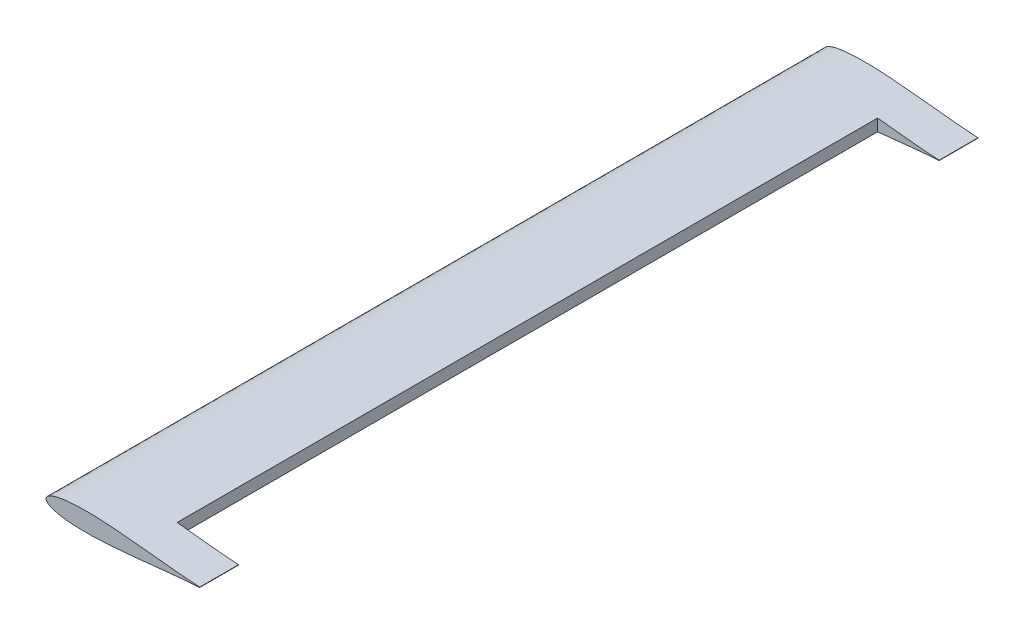
SolidWorks part; units mm, degrees
other "Markup1"
sketch "Sketch3" plane through (-0.0553, -7.355, 609.6) normal (0, 0, 1) x (1, 0, 0)
ref_plane "Front Plane" through (0, 0, 0) normal (0, 0, 1) x (1, 0, 0)
ref_plane "Top Plane" through (0, 0, 0) normal (0, 1, 0) x (1, 0, 0)
ref_plane "Right Plane" through (0, 0, 0) normal (1, 0, 0) x (0, 0, -1)
curve "Curve1"
  spline degree 3 poles (25.3337, -0.0003, 0) (25.4166, 0, 0) (25.3337, 0.0003, 0) (25.2654, 0.0018, 0) (25.098, 0.0055, 0) (24.8899, 0.0127, 0) (24.614, 0.0243, 0) (24.2833, 0.0411, 0) (23.8951, 0.064, 0) (23.4526, 0.0935, 0) (22.9577, 0.1302, 0) (22.4128, 0.1742, 0) (21.8206, 0.2257, 0) (21.184, 0.2845, 0) (20.5061, 0.3502, 0) (19.7901, 0.4224, 0) (19.0396, 0.5004, 0) (18.2582, 0.5832, 0) (17.4498, 0.6697, 0) (16.6182, 0.7589, 0) (15.7675, 0.8494, 0) (14.9019, 0.9396, 0) (14.0255, 1.0282, 0) (13.1427, 1.1135, 0) (12.2578, 1.1941, 0) (11.3749, 1.2683, 0) (10.4986, 1.3345, 0) (9.6329, 1.3915, 0) (8.7821, 1.4377, 0) (7.9504, 1.4721, 0) (7.1418, 1.4935, 0) (6.3603, 1.501, 0) (5.6096, 1.4941, 0) (4.8934, 1.4721, 0) (4.2152, 1.4349, 0) (3.5783, 1.3824, 0) (2.9857, 1.3149, 0) (2.4403, 1.233, 0) (1.9447, 1.1371, 0) (1.5013, 1.0283, 0) (1.1121, 0.9078, 0) (0.7787, 0.7769, 0) (0.5025, 0.6369, 0) (0.2843, 0.4891, 0) (0.1244, 0.334, 0) (0.024, 0.1711, 0) (-0.0113, 0, 0) (0.024, -0.1711, 0) (0.1244, -0.334, 0) (0.2843, -0.4891, 0) (0.5025, -0.6369, 0) (0.7787, -0.7769, 0) (1.1121, -0.9078, 0) (1.5013, -1.0283, 0) (1.9447, -1.1371, 0) (2.4403, -1.233, 0) (2.9857, -1.3149, 0) (3.5783, -1.3824, 0) (4.2152, -1.4349, 0) (4.8934, -1.4721, 0) (5.6096, -1.4941, 0) (6.3603, -1.501, 0) (7.1418, -1.4935, 0) (7.9504, -1.4721, 0) (8.7821, -1.4377, 0) (9.6329, -1.3915, 0) (10.4986, -1.3345, 0) (11.3749, -1.2683, 0) (12.2578, -1.1941, 0) (13.1427, -1.1135, 0) (14.0255, -1.0282, 0) (14.9019, -0.9396, 0) (15.7675, -0.8494, 0) (16.6182, -0.7589, 0) (17.4498, -0.6697, 0) (18.2582, -0.5832, 0) (19.0396, -0.5004, 0) (19.7901, -0.4224, 0) (20.5061, -0.3502, 0) (21.184, -0.2845, 0) (21.8206, -0.2257, 0) (22.4128, -0.1742, 0) (22.9577, -0.1302, 0) (23.4526, -0.0935, 0) (23.8951, -0.064, 0) (24.2833, -0.0411, 0) (24.614, -0.0243, 0) (24.8899, -0.0127, 0) (25.098, -0.0055, 0) (25.2654, -0.0018, 0) (25.3337, -0.0003, 0) (25.4166, 0, 0) (25.3337, 0.0003, 0) knots -0.005355 -0.002385 -0.000597 0 0.000597 0.002385 0.005355 0.009495 0.014784 0.021198 0.028708 0.037278 0.046868 0.05743 0.068917 0.081271 0.094432 0.108338 0.122919 0.138103 0.153815 0.169978 0.186509 0.203327 0.220349 0.237488 0.25466 0.271779 0.288763 0.305527 0.32199 0.338073 0.353702 0.368803 0.383306 0.397149 0.410269 0.422614 0.434133 0.444783 0.454527 0.463337 0.471194 0.478092 0.484042 0.489082 0.493295 0.496842 0.5 0.503158 0.506705 0.510918 0.515958 0.521908 0.528806 0.536663 0.545473 0.555218 0.565867 0.577386 0.589731 0.602851 0.616694 0.631197 0.646298 0.661927 0.67801 0.694473 0.711237 0.728221 0.74534 0.762512 0.779651 0.796673 0.813491 0.830023 0.846185 0.861897 0.877081 0.891662 0.905568 0.918729 0.931083 0.94257 0.953133 0.962722 0.971292 0.978802 0.985216 0.990505 0.994645 0.997615 0.999403 1 1.000597 1.002385 1.005355 periodic
sketch "Sketch2" plane through (0, 0, 0) normal (0, 0, 1) x (1, 0, 0)
  line L0 (0, 0) -> (25.4, 0) construction
  line L1 (0, 0) -> (124.46, 0) construction
  line L2 (120.381, 0.1319) -> (120.381, -0.1319)
  line L3 (62.23, 0) -> (62.23, 5.6527) construction
  spline S0 degree 3 poles (25.3337, -0.0003) (25.4166, 0) (25.3337, 0.0003) (25.2654, 0.0018) (25.098, 0.0055) (24.8899, 0.0127) (24.614, 0.0243) (24.2833, 0.0411) (23.8951, 0.064) (23.4526, 0.0935) (22.9577, 0.1302) (22.4128, 0.1742) (21.8206, 0.2257) (21.184, 0.2845) (20.5061, 0.3502) (19.7901, 0.4224) (19.0396, 0.5004) (18.2582, 0.5832) (17.4498, 0.6697) (16.6182, 0.7589) (15.7675, 0.8494) (14.9019, 0.9396) (14.0255, 1.0282) (13.1427, 1.1135) (12.2578, 1.1941) (11.3749, 1.2683) (10.4986, 1.3345) (9.6329, 1.3915) (8.7821, 1.4377) (7.9504, 1.4721) (7.1418, 1.4935) (6.3603, 1.501) (5.6096, 1.4941) (4.8934, 1.4721) (4.2152, 1.4349) (3.5783, 1.3824) (2.9857, 1.3149) (2.4403, 1.233) (1.9447, 1.1371) (1.5013, 1.0283) (1.1121, 0.9078) (0.7787, 0.7769) (0.5025, 0.6369) (0.2843, 0.4891) (0.1244, 0.334) (0.024, 0.1711) (-0.0113, 0) (0.024, -0.1711) (0.1244, -0.334) (0.2843, -0.4891) (0.5025, -0.6369) (0.7787, -0.7769) (1.1121, -0.9078) (1.5013, -1.0283) (1.9447, -1.1371) (2.4403, -1.233) (2.9857, -1.3149) (3.5783, -1.3824) (4.2152, -1.4349) (4.8934, -1.4721) (5.6096, -1.4941) (6.3603, -1.501) (7.1418, -1.4935) (7.9504, -1.4721) (8.7821, -1.4377) (9.6329, -1.3915) (10.4986, -1.3345) (11.3749, -1.2683) (12.2578, -1.1941) (13.1427, -1.1135) (14.0255, -1.0282) (14.9019, -0.9396) (15.7675, -0.8494) (16.6182, -0.7589) (17.4498, -0.6697) (18.2582, -0.5832) (19.0396, -0.5004) (19.7901, -0.4224) (20.5061, -0.3502) (21.184, -0.2845) (21.8206, -0.2257) (22.4128, -0.1742) (22.9577, -0.1302) (23.4526, -0.0935) (23.8951, -0.064) (24.2833, -0.0411) (24.614, -0.0243) (24.8899, -0.0127) (25.098, -0.0055) (25.2654, -0.0018) (25.3337, -0.0003) (25.4166, 0) (25.3337, 0.0003) knots -0.005355 -0.002385 -0.000597 0 0.000597 0.002385 0.005355 0.009495 0.014784 0.021198 0.028708 0.037278 0.046868 0.05743 0.068917 0.081271 0.094432 0.108338 0.122919 0.138103 0.153815 0.169978 0.186509 0.203327 0.220349 0.237488 0.25466 0.271779 0.288763 0.305527 0.32199 0.338073 0.353702 0.368803 0.383306 0.397149 0.410269 0.422614 0.434133 0.444783 0.454527 0.463337 0.471194 0.478092 0.484042 0.489082 0.493295 0.496842 0.5 0.503158 0.506705 0.510918 0.515958 0.521908 0.528806 0.536663 0.545473 0.555218 0.565867 0.577386 0.589731 0.602851 0.616694 0.631197 0.646298 0.661927 0.67801 0.694473 0.711237 0.728221 0.74534 0.762512 0.779651 0.796673 0.813491 0.830023 0.846185 0.861897 0.877081 0.891662 0.905568 0.918729 0.931083 0.94257 0.953133 0.962722 0.971292 0.978802 0.985216 0.990505 0.994645 0.997615 0.999403 1 1.000597 1.002385 1.005355 only from (25.4, 0) to (25.4, 0) construction
  spline S1 degree 3 poles (25.3337, -0.0003) (25.4166, 0) (25.3337, 0.0003) (25.2654, 0.0018) (25.098, 0.0055) (24.8899, 0.0127) (24.614, 0.0243) (24.2833, 0.0411) (23.8951, 0.064) (23.4526, 0.0935) (22.9577, 0.1302) (22.4128, 0.1742) (21.8206, 0.2257) (21.184, 0.2845) (20.5061, 0.3502) (19.7901, 0.4224) (19.0396, 0.5004) (18.2582, 0.5832) (17.4498, 0.6697) (16.6182, 0.7589) (15.7675, 0.8494) (14.9019, 0.9396) (14.0255, 1.0282) (13.1427, 1.1135) (12.2578, 1.1941) (11.3749, 1.2683) (10.4986, 1.3345) (9.6329, 1.3915) (8.7821, 1.4377) (7.9504, 1.4721) (7.1418, 1.4935) (6.3603, 1.501) (5.6096, 1.4941) (4.8934, 1.4721) (4.2152, 1.4349) (3.5783, 1.3824) (2.9857, 1.3149) (2.4403, 1.233) (1.9447, 1.1371) (1.5013, 1.0283) (1.1121, 0.9078) (0.7787, 0.7769) (0.5025, 0.6369) (0.2843, 0.4891) (0.1244, 0.334) (0.024, 0.1711) (-0.0113, 0) (0.024, -0.1711) (0.1244, -0.334) (0.2843, -0.4891) (0.5025, -0.6369) (0.7787, -0.7769) (1.1121, -0.9078) (1.5013, -1.0283) (1.9447, -1.1371) (2.4403, -1.233) (2.9857, -1.3149) (3.5783, -1.3824) (4.2152, -1.4349) (4.8934, -1.4721) (5.6096, -1.4941) (6.3603, -1.501) (7.1418, -1.4935) (7.9504, -1.4721) (8.7821, -1.4377) (9.6329, -1.3915) (10.4986, -1.3345) (11.3749, -1.2683) (12.2578, -1.1941) (13.1427, -1.1135) (14.0255, -1.0282) (14.9019, -0.9396) (15.7675, -0.8494) (16.6182, -0.7589) (17.4498, -0.6697) (18.2582, -0.5832) (19.0396, -0.5004) (19.7901, -0.4224) (20.5061, -0.3502) (21.184, -0.2845) (21.8206, -0.2257) (22.4128, -0.1742) (22.9577, -0.1302) (23.4526, -0.0935) (23.8951, -0.064) (24.2833, -0.0411) (24.614, -0.0243) (24.8899, -0.0127) (25.098, -0.0055) (25.2654, -0.0018) (25.3337, -0.0003) (25.4166, 0) (25.3337, 0.0003) knots -0.005355 -0.002385 -0.000597 0 0.000597 0.002385 0.005355 0.009495 0.014784 0.021198 0.028708 0.037278 0.046868 0.05743 0.068917 0.081271 0.094432 0.108338 0.122919 0.138103 0.153815 0.169978 0.186509 0.203327 0.220349 0.237488 0.25466 0.271779 0.288763 0.305527 0.32199 0.338073 0.353702 0.368803 0.383306 0.397149 0.410269 0.422614 0.434133 0.444783 0.454527 0.463337 0.471194 0.478092 0.484042 0.489082 0.493295 0.496842 0.5 0.503158 0.506705 0.510918 0.515958 0.521908 0.528806 0.536663 0.545473 0.555218 0.565867 0.577386 0.589731 0.602851 0.616694 0.631197 0.646298 0.661927 0.67801 0.694473 0.711237 0.728221 0.74534 0.762512 0.779651 0.796673 0.813491 0.830023 0.846185 0.861897 0.877081 0.891662 0.905568 0.918729 0.931083 0.94257 0.953133 0.962722 0.971292 0.978802 0.985216 0.990505 0.994645 0.997615 0.999403 1 1.000597 1.002385 1.005355 only from (25.4, 0) to (25.4, 0) construction
  spline S2 degree 3 poles (120.381, 0.1319) (119.9463, 0.1527) (118.8798, 0.2078) (117.0858, 0.3137) (114.9178, 0.4584) (112.4927, 0.6382) (109.8228, 0.8537) (106.9211, 1.106) (103.8017, 1.394) (100.4797, 1.7159) (96.9715, 2.0698) (93.294, 2.4518) (89.4653, 2.8575) (85.5038, 3.2818) (81.4291, 3.7187) (77.2608, 4.162) (73.0193, 4.6041) (68.7252, 5.0383) (64.3994, 5.4564) (60.0631, 5.8512) (55.7372, 6.2145) (51.4429, 6.5392) (47.2011, 6.8181) (43.0324, 7.0448) (38.9571, 7.2131) (34.9951, 7.3181) (31.1655, 7.355) (27.4872, 7.3209) (23.9779, 7.2133) (20.6546, 7.0309) (17.5336, 6.7739) (14.6298, 6.4432) (11.9574, 6.0415) (9.5291, 5.5718) (7.3563, 5.0389) (5.4492, 4.4484) (3.8158, 3.8067) (2.4624, 3.1207) (1.3928, 2.3964) (0.6096, 1.6368) (0.1174, 0.8384) (-0.0553, 0) (0.1174, -0.8384) (0.6096, -1.6368) (1.3928, -2.3964) (2.4624, -3.1207) (3.8158, -3.8067) (5.4492, -4.4484) (7.3563, -5.0389) (9.5291, -5.5718) (11.9574, -6.0415) (14.6299, -6.4433) (17.5336, -6.7739) (20.6546, -7.0309) (23.9779, -7.2133) (27.4872, -7.3209) (31.1655, -7.355) (34.9951, -7.3181) (38.9571, -7.2131) (43.0324, -7.0448) (47.2011, -6.8181) (51.4429, -6.5392) (55.7372, -6.2145) (60.0631, -5.8512) (64.3994, -5.4564) (68.7252, -5.0383) (73.0193, -4.6041) (77.2608, -4.162) (81.4291, -3.7187) (85.5039, -3.2817) (89.4653, -2.8575) (93.294, -2.4518) (96.9715, -2.0698) (100.4797, -1.7159) (103.8017, -1.394) (106.9211, -1.106) (109.8228, -0.8537) (112.4927, -0.6382) (114.9179, -0.4584) (117.0858, -0.3137) (118.8798, -0.2078) (119.9463, -0.1527) (120.381, -0.1319) knots 0.016066 0.016066 0.016066 0.016066 0.021198 0.028708 0.037278 0.046868 0.05743 0.068917 0.081271 0.094432 0.108338 0.122919 0.138103 0.153815 0.169978 0.186509 0.203327 0.220349 0.237488 0.25466 0.271779 0.288763 0.305527 0.32199 0.338073 0.353702 0.368803 0.383306 0.397149 0.410269 0.422614 0.434133 0.444783 0.454527 0.463337 0.471194 0.478092 0.484042 0.489082 0.493295 0.496842 0.5 0.503158 0.506705 0.510918 0.515958 0.521908 0.528806 0.536663 0.545473 0.555218 0.565867 0.577386 0.589731 0.602851 0.616694 0.631197 0.646298 0.661927 0.67801 0.694473 0.711237 0.728221 0.74534 0.762512 0.779651 0.796673 0.813491 0.830023 0.846185 0.861897 0.877081 0.891662 0.905568 0.918729 0.931083 0.94257 0.953133 0.962722 0.971292 0.978802 0.983934 0.983934 0.983934 0.983934
  point P8 (0, 0)
  dimension "D1" = 124.46
  dimension "D2" = 4.079
  dimension "D3" = 5.6527
extrude "Boss-Extrude4" add sketch "Sketch2" along normal blind 609.6
sketch "Sketch4" plane through (0, 0, 0) normal (0, 1, 0) x (1, 0, 0)
  line L0 (0, 0) -> (0, -609.6) construction
  line L1 (0, -304.8) -> (120.381, -304.8) construction
  line L2 (120.381, -609.6) -> (120.381, 0) construction
  line L3 (120.381, -304.8) -> (72.2327, -304.8)
  line L4 (72.2327, -579.12) -> (72.2327, -30.48)
  line L5 (72.2327, -30.48) -> (171.5692, -30.48)
  line L6 (171.5692, -30.48) -> (171.5692, -579.12)
  line L7 (171.5692, -579.12) -> (72.2327, -579.12)
  point P12 (72.2327, -304.8)
  dimension "D1" = 48.1482
  dimension "D2" = 548.64
extrude "Cut-Extrude1" cut sketch "Sketch4" against normal through all both and the other way through all contours L7 L6 L5 L4 region at (121.901, 0, 304.8)
sketch "Sketch5" plane through (0, 0, 30.48) normal (0, 0, 1) x (1, 0, 0)
  line L0 (72.2327, 4.6824) -> (72.2327, -4.6824)
  line L1 (72.2327, 0) -> (120.381, 0) construction
  line L2 (120.381, -0.1319) -> (120.381, 0.1319) construction
  circle A0 centre (76.3067, 0) radius 4.0739 construction
  dimension "D1" = 8.1479
